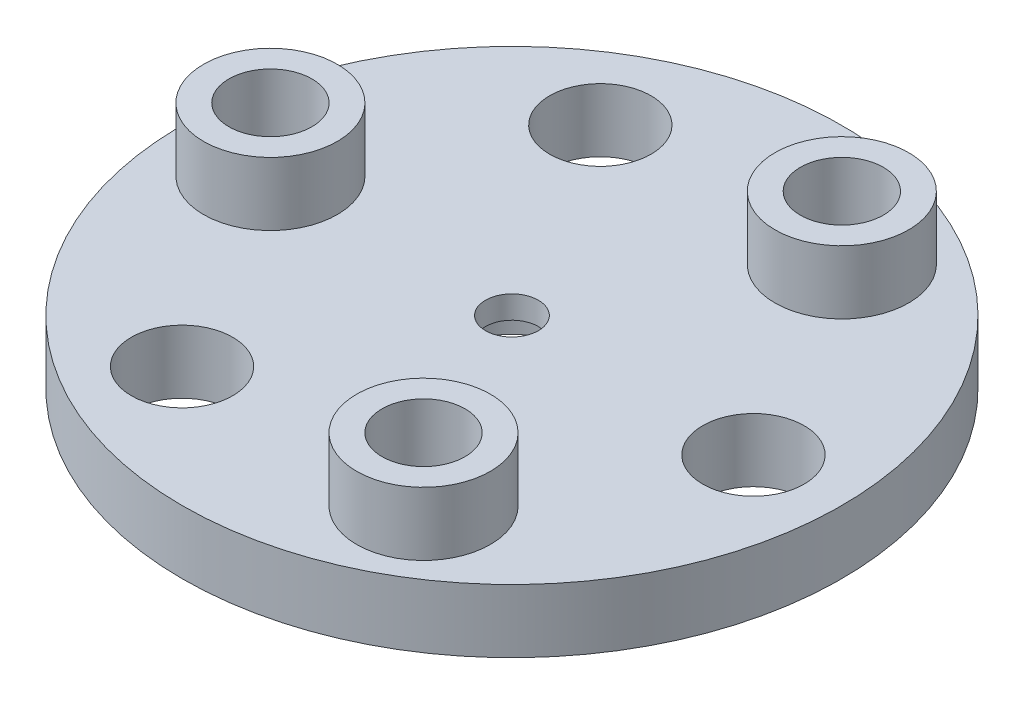
SolidWorks part; units mm, degrees
ref_plane "Front Plane" through (0, 0, 0) normal (0, 0, 1) x (1, 0, 0)
ref_plane "Top Plane" through (0, 0, 0) normal (0, 1, 0) x (1, 0, 0)
ref_plane "Right Plane" through (0, 0, 0) normal (1, 0, 0) x (0, 0, -1)
sketch "Sketch2" plane through (0, 0, 0) normal (0, 1, 0) x (1, 0, 0)
  circle A0 centre (0, 0) radius 26
  circle A1 centre (0, 0) radius 2.0856
  point P11 (0, 0)
  dimension "D1" = 52
extrude "Boss-Extrude2" add sketch "Sketch2" along normal blind 10
sketch "Sketch3" plane through (0, 10, 0) normal (0, -1, 0) x (1, 0, 0)
  circle A3 centre (9.5263, -16.4999) radius 3.275
  circle A4 centre (9.5263, 16.4999) radius 3.275
  circle A5 centre (-19.0525, 0) radius 3.275
  circle A6 centre (9.5263, -16.4999) radius 3.175 construction
  circle A7 centre (-19.0525, 0) radius 3.175 construction
  circle A8 centre (9.5263, 16.4999) radius 3.175 construction
  dimension "D1" = 6.55
  dimension "D2" = 6.55
  dimension "D3" = 6.55
extrude "Cut-Extrude1" cut sketch "Sketch3" along normal blind 7.5
sketch "Sketch4" plane through (0, 10, 0) normal (0, 1, 0) x (1, 0, 0)
  arc A23 (-13.7775, 0) -> (-13.7775, 0) centre (-19.0525, 0) ccw
  circle A24 centre (-19.0525, 0) radius 5.275
  arc A30 (14.8013, -16.4999) -> (14.8013, -16.4999) centre (9.5263, -16.4999) ccw
  circle A31 centre (9.5263, -16.4999) radius 5.275
  circle A32 centre (0, 0) radius 26 construction
  arc A33 (14.8012, 16.4999) -> (14.8012, 16.4999) centre (9.5263, 16.4999) ccw
  circle A34 centre (9.5263, 16.4999) radius 5.275
  circle A35 centre (0, 0) radius 26
  dimension "D1" = 2
  dimension "D2" = 2
  dimension "D3" = 2
extrude "Cut-Extrude2" cut sketch "Sketch4" against normal blind 5
sketch "Sketch5" plane through (0, 0, 0) normal (0, -1, 0) x (1, 0, 0)
  line L4 (4.064, -4.065) -> (-4.064, 4.065) construction
  line L5 (-4.064, -4.065) -> (4.064, 4.065) construction
  circle A1 centre (0, 0) radius 5.25
  point P1 (0, 0)
  dimension "D3" = 10.5
  dimension "D1" = 8.13
  dimension "D2" = 8.128
extrude "Cut-Extrude3" cut sketch "Sketch5" against normal blind 3.2
sketch "Sketch6" plane through (0, 5, 0) normal (0, 1, 0) x (1, 0, 0)
  circle A0 centre (-8.7331, 9.2208) radius 0.8
  circle A1 centre (9.2208, 8.7331) radius 0.8
  circle A2 centre (8.7331, -9.2208) radius 0.8
  circle A3 centre (-9.2208, -8.7331) radius 0.8
  point P12 (0, 0)
  dimension "D1" = 12.7
  dimension "D2" = 4
extrude "Cut-Extrude4" [suppressed] cut sketch "Sketch6" against normal through all both and the other way through all
sketch "Sketch7" [suppressed] plane through (0, 5, 0) normal (0, 1, 0) x (1, 0, 0)
  circle A0 centre (-8.7331, 9.2208) radius 1.5
  circle A1 centre (9.2208, 8.7331) radius 1.5
  circle A2 centre (8.7331, -9.2208) radius 1.5
  circle A3 centre (-9.2208, -8.7331) radius 1.5
  point P12 (0, 0)
  dimension "D1" = 4
  dimension "D2" = 3
extrude "Cut-Extrude5" [suppressed] cut sketch "Sketch7" against normal blind 1
sketch "Sketch8" plane through (0, 5, 0) normal (0, 1, 0) x (1, 0, 0)
  circle A4 centre (-9.5262, -16.4999) radius 4
  circle A8 centre (-9.5262, 16.4999) radius 4
  circle A12 centre (19.0525, 0) radius 4
  point P24 (0, 0)
  dimension "D1" = 8
  dimension "D2" = 8
  dimension "D3" = 8
extrude "Cut-Extrude6" cut sketch "Sketch8" against normal through all
